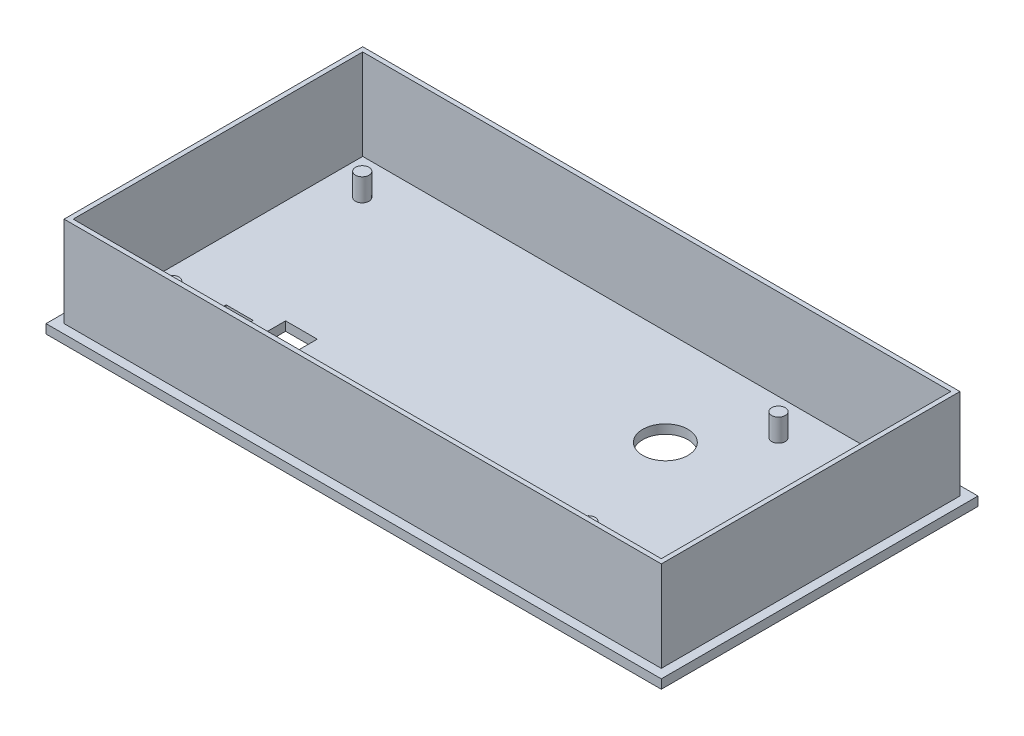
SolidWorks part; units mm, degrees
ref_plane "前视基准面" through (0, 0, 0) normal (0, 0, 1) x (1, 0, 0)
ref_plane "上视基准面" through (0, 0, 0) normal (0, 1, 0) x (1, 0, 0)
ref_plane "右视基准面" through (0, 0, 0) normal (1, 0, 0) x (0, 0, -1)
other "Configuration Table"
sketch "草图1" plane through (0, 0, 0) normal (0, 1, 0) x (1, 0, 0)
  line L1 (68, -35) -> (-68, -35)
  line L2 (68, -35) -> (68, 35)
  line L3 (68, 35) -> (-68, 35)
  line L4 (-68, -35) -> (-68, 35)
  line L5 (68, -35) -> (-68, 35) construction
  line L6 (68, 35) -> (-68, -35) construction
  point P0 (0, 0)
  dimension "D1" = 70
  dimension "D2" = 136
extrude "凸台-拉伸1" add sketch "草图1" along normal blind 2
sketch "草图2" plane through (0, 2, 0) normal (0, 1, 0) x (1, 0, 0)
  line L6 (65, -32) -> (-65, -32)
  line L7 (-66, 33) -> (66, 33)
  line L8 (-66, 33) -> (-66, -33)
  line L9 (-66, -33) -> (66, -33)
  line L10 (66, 33) -> (66, -33)
  line L11 (65, -32) -> (65, 32)
  line L12 (65, 32) -> (-65, 32)
  line L13 (-65, -32) -> (-65, 32)
  line L14 (65, -32) -> (-65, 32) construction
  line L15 (65, 32) -> (-65, -32) construction
  point P2 (0, 0)
  dimension "D1" = 132
  dimension "D2" = 66
  dimension "D3" = 130
  dimension "D4" = 64
extrude "凸台-拉伸2" add sketch "草图2" along normal blind 20
sketch "草图3" plane through (0, 2, 0) normal (0, 1, 0) x (1, 0, 0)
  line L0 (-61.2128, 3.1099) -> (38.7872, 3.1099) construction
  line L1 (-61.2128, 28.1099) -> (38.7872, 28.1099)
  line L2 (-61.2128, 28.1099) -> (-61.2128, -21.8901)
  line L3 (-61.2128, -21.8901) -> (38.7872, -21.8901)
  line L4 (38.7872, 28.1099) -> (38.7872, -21.8901)
  line L5 (-11.2128, 28.1099) -> (-11.2128, -21.8901) construction
  circle A0 centre (-57.2128, 24.1099) radius 1.5
  circle A1 centre (-57.2128, -17.8901) radius 1.5
  circle A2 centre (34.7872, -17.8901) radius 1.5
  circle A3 centre (34.7872, 24.1099) radius 1.5
  dimension "D3" = 4
  dimension "D4" = 4
  dimension "D5" = 3
  dimension "D1" = 100
  dimension "D2" = 50
extrude "凸台-拉伸3" add sketch "草图3" along normal blind 5 contours A0 | A1 | A2 | A3
sketch "草图5" plane through (0, 2, 0) normal (0, 1, 0) x (1, 0, 0)
  line L0 (23.1784, 23.2209) -> (23.1784, 10.7209) construction
  circle A0 centre (23.1784, 10.7209) radius 5
  dimension "D1" = 12.5
extrude "切除-拉伸2" cut sketch "草图5" against normal through all
sketch "草图6" plane through (0, 2, 0) normal (0, 1, 0) x (1, 0, 0)
  line L0 (-51.701, -14.4981) -> (-51.701, -11.4981)
  line L1 (-51.701, -14.4981) -> (-51.701, -17.4981)
  line L2 (-51.701, -11.4981) -> (-45.701, -11.4981)
  line L3 (-45.701, -11.4981) -> (-45.701, -17.4981)
  line L4 (-45.701, -17.4981) -> (-51.701, -17.4981)
  circle A0 centre (-51.2438, -14.4981) radius 0.4572 construction
  dimension "D1" = 3
  dimension "D2" = 3
  dimension "D3" = 6
  dimension "D4" = 6
extrude "切除-拉伸3" cut sketch "草图6" against normal through all
sketch "草图7" plane through (0, 2, 0) normal (0, 1, 0) x (1, 0, 0)
  line L0 (-38.5437, -15.0481) -> (-38.5437, -13.9481) construction
  line L1 (-37.8938, -15.0481) -> (-39.1937, -15.0481) construction
  line L2 (-39.1937, -13.9481) -> (-37.8938, -13.9481) construction
  line L3 (-38.5437, -14.4981) -> (-38.5437, -7.9981) construction
  line L8 (-38.5437, -7.9981) -> (-42.0437, -7.9981)
  line L9 (-42.0437, -7.9981) -> (-42.0437, -20.9981)
  line L10 (-42.0437, -20.9981) -> (-35.0437, -20.9981)
  line L11 (-35.0437, -20.9981) -> (-35.0437, -7.9981)
  line L12 (-35.0437, -7.9981) -> (-38.5437, -7.9981)
  dimension "D1" = 13
  dimension "D2" = 3.5
extrude "切除-拉伸4" cut sketch "草图7" against normal through all
